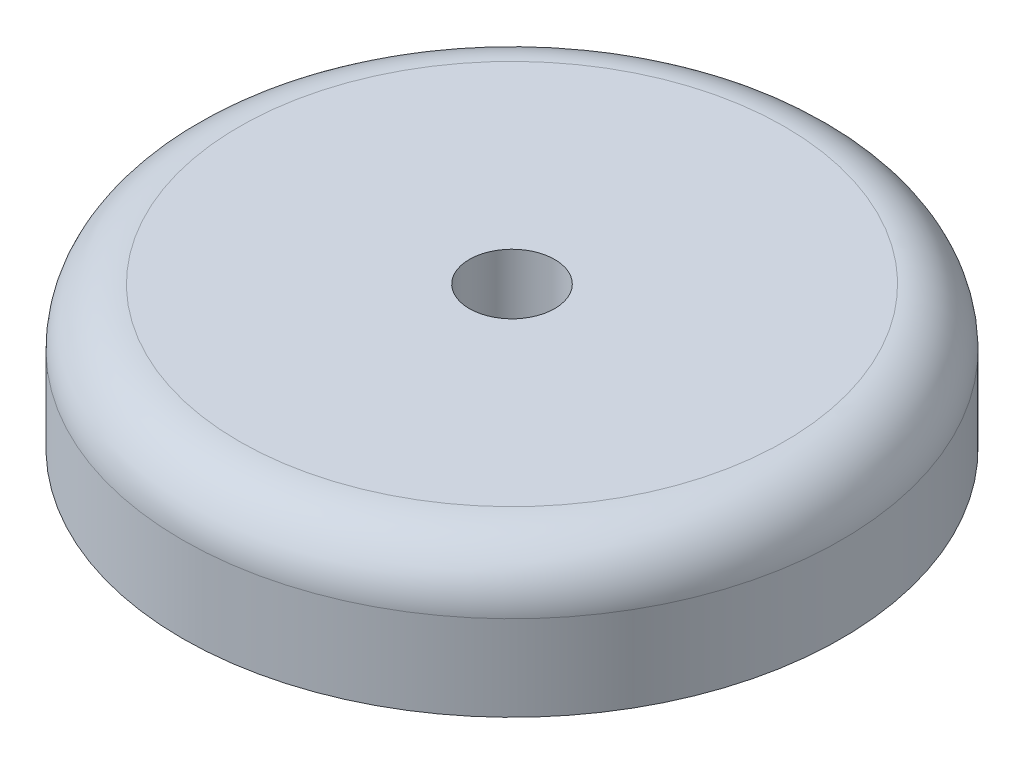
SolidWorks part; units mm, degrees
ref_plane "Front Plane" through (0, 0, 0) normal (0, 0, 1) x (1, 0, 0)
ref_plane "Top Plane" through (0, 0, 0) normal (0, 1, 0) x (1, 0, 0)
ref_plane "Right Plane" through (0, 0, 0) normal (1, 0, 0) x (0, 0, -1)
sketch "Sketch1" plane through (0, 0, 0) normal (0, 1, 0) x (1, 0, 0)
  circle A0 centre (0, 0) radius 14 construction
  circle A1 centre (0, 0) radius 1.5
  circle A2 centre (0, 0) radius 11.587
  dimension "D1" = 28
  dimension "D2" = 2.413
  dimension "D3" = 3
extrude "Boss-Extrude1" add sketch "Sketch1" along normal blind 5
fillet "Fillet1" radius 2 1 edges at (0, 5, 11.587)
